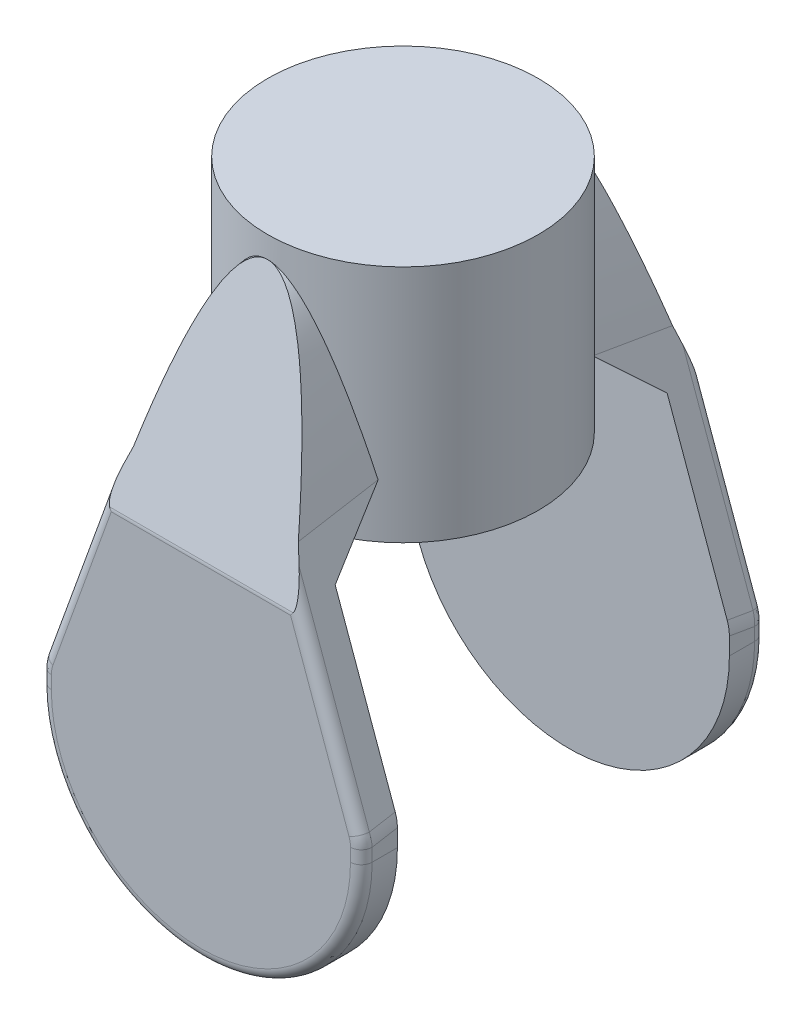
SolidWorks part; units mm, degrees
ref_plane "Front Plane" through (0, 0, 0) normal (0, 0, 1) x (1, 0, 0)
ref_plane "Top Plane" through (0, 0, 0) normal (0, 1, 0) x (1, 0, 0)
ref_plane "Right Plane" through (0, 0, 0) normal (1, 0, 0) x (0, 0, -1)
sketch "Sketch1" plane through (0, 0, 0) normal (0, 1, 0) x (1, 0, 0)
  circle A0 centre (0, 0) radius 37.5
  dimension "D1" = 75
extrude "Boss-Extrude1" add sketch "Sketch1" along normal blind 76.2
sketch "Sketch2" plane through (0, 0, 0) normal (1, 0, 0) x (0, 0, -1)
  line L0 (-46, 0) -> (-46, -88.9)
  line L1 (-46, -88.9) -> (-56, -88.9)
  line L2 (-56, -88.9) -> (-56, 6.9306)
  line L3 (-56, 6.9306) -> (-37.5, 70.2065)
  line L4 (-37.5, 76.2) -> (-37.5, 0) construction
  line L5 (-37.5, 70.2065) -> (-29.7398, 24.8975)
  line L6 (-29.7398, 24.8975) -> (-46, 0) construction
  line L7 (-37.5, 0) -> (37.5, 0) construction
  line L8 (-46, 0) -> (-46, 9.9944)
  line L9 (-46, 9.9944) -> (-29.7398, 24.8975)
  point P8 (-29.7398, 24.8975)
  dimension "D1" = 88.9
  dimension "D2" = 10
  dimension "D3" = 46
extrude "Boss-Extrude2" add sketch "Sketch2" along normal blind 44.45 and the other way blind 44.45
sketch "Sketch3" plane through (0, 0, 56) normal (0, 0, 1) x (1, 0, 0)
  line L0 (-44.45, 6.9306) -> (-44.45, -88.9) construction
  line L1 (44.45, 6.9306) -> (44.45, -88.9) construction
  line L2 (-44.45, -88.9) -> (44.45, -88.9) construction
  line L3 (-44.45, -44.45) -> (-117.2331, -65.9707)
  line L4 (-117.2331, -65.9707) -> (28.9838, -131.2925)
  line L5 (28.9838, -131.2925) -> (111.1768, -87.6004)
  line L6 (111.1768, -87.6004) -> (44.45, -44.45)
  arc A0 (-44.45, -44.45) -> (44.45, -44.45) centre (0, -44.45) ccw
extrude "Cut-Extrude1" cut sketch "Sketch3" against normal blind 38.1
sketch "Sketch4" plane through (0, -4.2389, 24.7496) normal (0, 0.1688, -0.9856) x (-1, 0, 0)
  line L0 (22.8428, 29.5606) -> (49.8987, -44.466)
  line L1 (49.8987, -44.466) -> (74.001, 56.8824)
  line L2 (74.001, 56.8824) -> (49.8987, 87.3946)
  line L3 (49.8987, 87.3946) -> (0, 75.5294)
  ellipse E0 centre (0, -146.6083) end of major axis (0, -368.7461) minor radius 37.5 (22.8428, 29.5606) -> (0, 75.5294) ccw construction
  ellipse E1 centre (0, -146.6083) end of major axis (0, -368.7461) minor radius 37.5 (22.8428, 29.5606) -> (0, 75.5294) ccw
extrude "Cut-Extrude2" cut sketch "Sketch4" against normal blind 38.1
mirror "Mirror1" about plane through (0, 0, 0) normal (1, 0, 0) of "Cut-Extrude2"
fillet "Fillet2" radius 10 2 edges at (-44.45, -38.7232, 51) (44.45, -38.7232, 51)
mirror "Mirror2" about plane through (0, 0, 0) normal (0, 0, 1) of "Boss-Extrude2", "Cut-Extrude1", "Cut-Extrude2", "Mirror1", "Fillet2"
ref_axis "Shoulder Roll" through (0, 85.1682, 0) along (0, -1, 0)
ref_axis "Shoulder Pitch" through (0, -44.45, 46) along (0, 0, 1)
sketch "Sketch5" plane through (0, 0, 0) normal (0, -1, 0) x (1, 0, 0)
  circle A0 centre (0, 0) radius 37.5 construction
  circle A1 centre (0, 0) radius 37.5
extrude "Cut-Extrude3" cut sketch "Sketch5" against normal blind 10
fillet "Fillet7" radius 3 16 edges at (0, -88.9, -56) (44.45, -42.9128, -56) (44.2969, -39.6071, -56) (35.7687, -15.4811, -56) (0, 6.9306, -56) (-35.7687, -15.4811, -56) (-44.2969, -39.6071, -56) (-44.45, -42.9128, -56) (0, 6.9306, 56) (35.7687, -15.4811, 56) (44.2969, -39.6071, 56) (44.45, -42.9128, 56) (0, -88.9, 56) (-44.45, -42.9128, 56) (-44.2969, -39.6071, 56) (-35.7687, -15.4811, 56)
